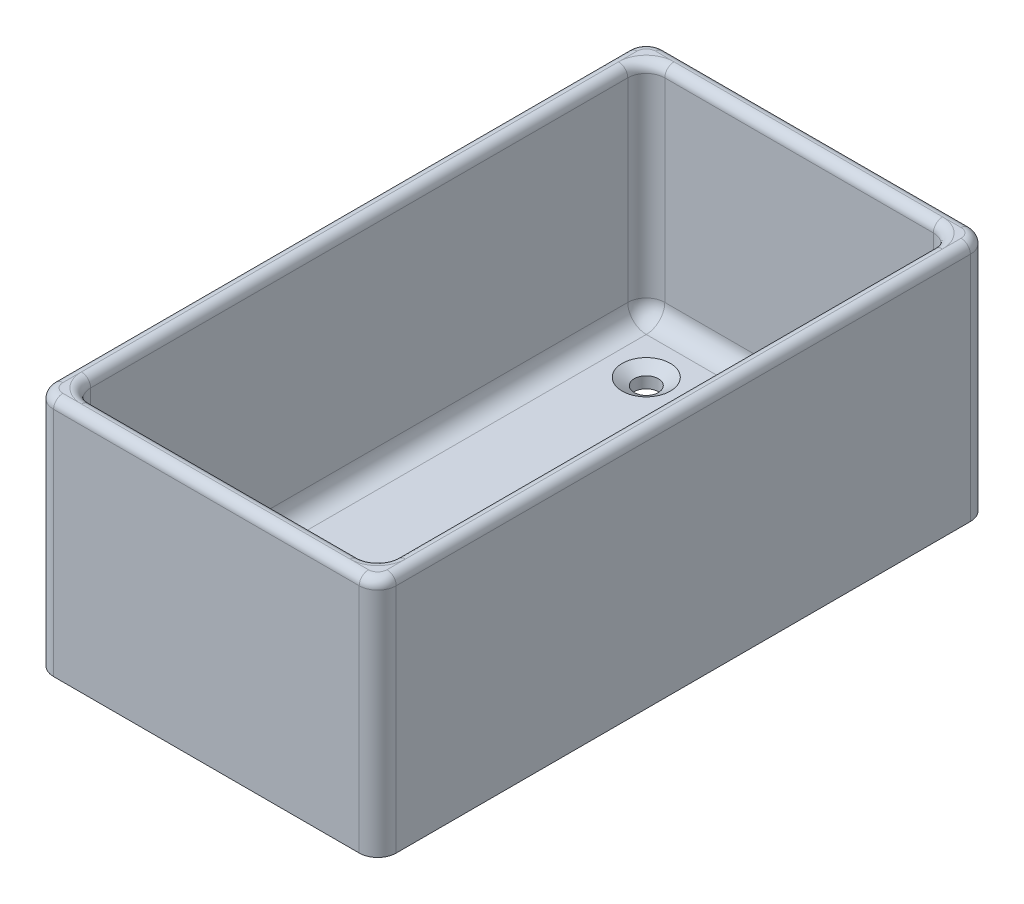
SolidWorks part; units mm, degrees
ref_plane "Front Plane" through (0, 0, 0) normal (0, 0, 1) x (1, 0, 0)
ref_plane "Top Plane" through (0, 0, 0) normal (0, 1, 0) x (1, 0, 0)
ref_plane "Right Plane" through (0, 0, 0) normal (1, 0, 0) x (0, 0, -1)
sketch "Sketch1" plane through (0, 0, 0) normal (0, 1, 0) x (1, 0, 0)
  line L1 (-26.1938, -49.2125) -> (26.1937, -49.2125)
  line L2 (-26.1938, -49.2125) -> (-26.1938, 49.2125)
  line L3 (-26.1938, 49.2125) -> (26.1937, 49.2125)
  line L4 (26.1937, -49.2125) -> (26.1937, 49.2125)
  line L5 (-26.1938, -49.2125) -> (26.1937, 49.2125) construction
  line L6 (-26.1938, 49.2125) -> (26.1937, -49.2125) construction
  point P0 (0, 0)
  dimension "D1" = 98.425
  dimension "D2" = 52.3875
extrude "Extrude-Thin1" add sketch "Sketch1" along normal blind 38.1 thin thin type one direction wall 3.175
fillet "Fillet1" radius 3.175 8 edges at (-26.1938, 19.05, 49.2125) (26.1937, 19.05, 49.2125) (26.1937, 19.05, -49.2125) (-26.1938, 19.05, -49.2125) (29.3687, 19.05, 52.3875) (-29.3688, 19.05, -52.3875) (29.3687, 19.05, -52.3875) (-29.3688, 19.05, 52.3875)
sketch "Sketch2" plane through (0, 0, 0) normal (0, -1, 0) x (1, 0, 0)
  line L4 (29.3687, -49.2125) -> (29.3687, 49.2125)
  line L5 (26.1937, 52.3875) -> (-26.1938, 52.3875)
  line L6 (-29.3687, 49.2125) -> (-29.3688, -49.2125)
  line L7 (-26.1938, -52.3875) -> (26.1937, -52.3875)
  line L8 (29.3687, -49.2125) -> (29.3687, 49.2125)
  line L9 (26.1937, 52.3875) -> (-26.1938, 52.3875)
  line L10 (-29.3687, 49.2125) -> (-29.3688, -49.2125)
  line L11 (-26.1938, -52.3875) -> (26.1937, -52.3875)
  arc A4 (29.3687, 49.2125) -> (26.1937, 52.3875) centre (26.1937, 49.2125) ccw
  arc A5 (-26.1938, 52.3875) -> (-29.3687, 49.2125) centre (-26.1938, 49.2125) ccw
  arc A6 (-29.3688, -49.2125) -> (-26.1938, -52.3875) centre (-26.1938, -49.2125) ccw
  arc A7 (26.1937, -52.3875) -> (29.3687, -49.2125) centre (26.1937, -49.2125) ccw
  arc A8 (29.3687, 49.2125) -> (26.1937, 52.3875) centre (26.1937, 49.2125) ccw
  arc A9 (-26.1938, 52.3875) -> (-29.3687, 49.2125) centre (-26.1938, 49.2125) ccw
  arc A10 (-29.3688, -49.2125) -> (-26.1938, -52.3875) centre (-26.1938, -49.2125) ccw
  arc A11 (26.1937, -52.3875) -> (29.3687, -49.2125) centre (26.1937, -49.2125) ccw
  dimension "D1" = 0
extrude "Boss-Extrude1" add sketch "Sketch2" along normal blind 3.175
fillet "Fillet2" radius 3.175 8 edges at (0, 0, -49.2125) (25.2638, 0, -48.2826) (26.1937, 0, 0) (25.2638, 0, 48.2826) (0, 0, 49.2125) (-25.2638, 0, 48.2826) (-26.1938, 0, 0) (-25.2638, 0, -48.2826)
sketch "Sketch3" plane through (0, 0, 0) normal (0, 1, 0) x (1, 0, 0)
  line L0 (-23.0187, 46.0375) -> (-16.6687, 39.6875) construction
  line L1 (0, 0) -> (-16.6687, 0) construction
  line L2 (0, 0) -> (0, 39.6875) construction
  line L3 (0, 39.6875) -> (-16.6687, 39.6875) construction
  line L4 (-16.6687, 0) -> (-16.6687, 39.6875) construction
  circle A0 centre (-16.6687, 39.6875) radius 2.0637
  dimension "D3" = 4.1275
  dimension "D1" = 135
  dimension "D2" = 6.35
extrude "Cut-Extrude1" cut sketch "Sketch3" against normal blind 3.175
ref_axis "Axis1" through (-16.6687, -3.175, -39.6875) along (0, 1, 0)
ref_plane "Plane1" through (0, 0, -39.6875) normal (0, 0, -1) x (0, 1, 0)
sketch "Sketch4" plane through (0, 0, -39.6875) normal (0, 0, -1) x (0, 1, 0)
  line L0 (-2.4801, -16.6687) -> (0, -12.5412)
  line L1 (-3.175, -16.6687) -> (0, -16.6687) construction
  line L2 (0, 23.0187) -> (0, -23.0187) construction
  line L3 (0, -12.5412) -> (0, -16.6687)
  line L4 (0, -16.6687) -> (-2.4801, -16.6687) construction
  line L5 (-2.4801, -16.6687) -> (0, -16.6687)
  dimension "D1" = 59
  dimension "D2" = 4.1275
revolve "Cut-Revolve1" cut sketch "Sketch4" angle 360 about L4
ref_axis "Axis2" through (0, 26.8287, 0) along (0, -1, 0)
pattern_circular "CirPattern1" count 2 over 360 about axis through (0, 26.8287, 0) along (0, -1, 0) of "Cut-Extrude1", "Cut-Revolve1"
fillet "Fillet3" radius 1.5875 16 edges at (28.4388, 38.1, -51.4576) (29.3687, 38.1, 0) (28.4388, 38.1, 51.4576) (0, 38.1, 52.3875) (-28.4388, 38.1, 51.4576) (-29.3688, 38.1, 0) (-28.4388, 38.1, -51.4576) (25.2638, 38.1, 48.2826) (0, 38.1, 49.2125) (-25.2638, 38.1, 48.2826) (-26.1938, 38.1, 0) (-25.2638, 38.1, -48.2826) (0, 38.1, -49.2125) (25.2638, 38.1, -48.2826) (0, 38.1, -52.3875) (26.1937, 38.1, 0)
